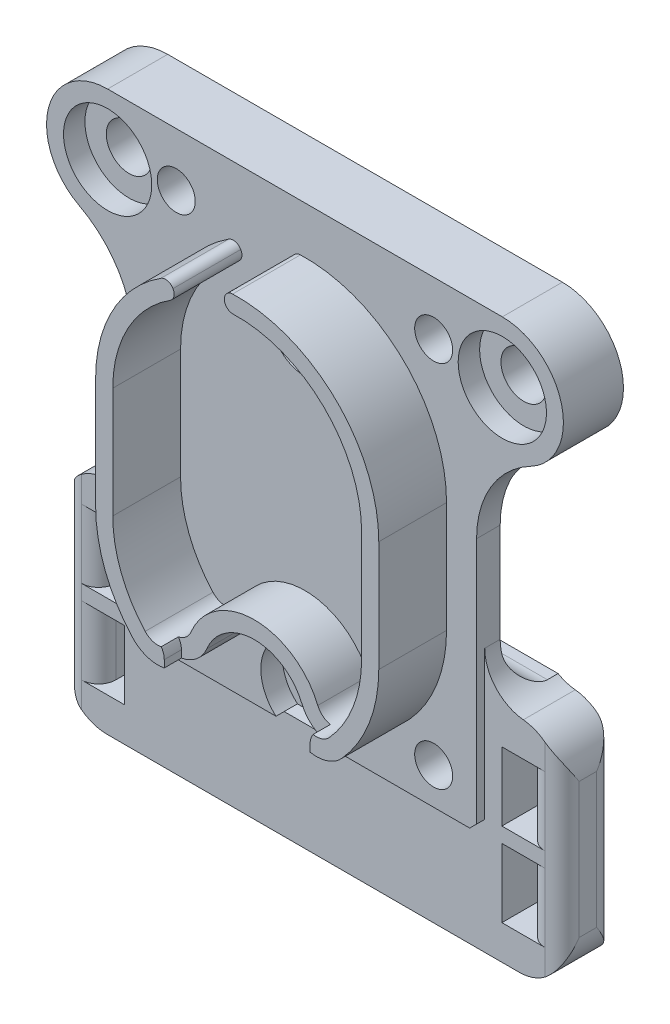
SolidWorks part; units mm, degrees
note: The reader was unsure of these and kept them because the rebuilt part matched: shared geometry of "Sketch12<3>".
ref_plane "Front Plane" through (0, 0, 0) normal (0, 0, 1) x (1, 0, 0)
ref_plane "Top Plane" through (0, 0, 0) normal (0, 1, 0) x (1, 0, 0)
ref_plane "Right Plane" through (0, 0, 0) normal (1, 0, 0) x (0, 0, -1)
sketch "Sketch1" plane through (0, 0, 0) normal (0, 0, 1) x (1, 0, 0)
  line L2 (55, 0) -> (-55, 0) construction
  line L4 (0, -8.5) -> (0, -21.398) construction
  line L6 (-5.5475, -31.3341) -> (-7.3967, -30.5721) construction
  line L15 (0, -9.2125) -> (0, 9.2125) construction
  line L16 (16.5, -8.5) -> (16.5, -21.398)
  line L17 (-16.5, -8.5) -> (-16.5, -21.398)
  line L18 (0, -8.5) -> (0, -21.398) construction
  line L19 (14.5, -8.5) -> (14.5, -21.398)
  line L20 (-14.5, -8.5) -> (-14.5, -21.398)
  line L21 (-12.2045, -32.5021) -> (-10.7252, -31.1561) construction
  line L22 (-10.7252, -31.1561) -> (-15.5979, -25.8005) construction
  line L23 (-7.3967, -30.5721) -> (-7.658, -31.2064) construction
  arc A23 (16.5, -8.5) -> (-16.5, -8.5) centre (0, -8.5) ccw
  arc A24 (-16.5, -21.398) -> (-12.2045, -32.5021) centre (0, -21.398) ccw
  arc A25 (14.5, -8.5) -> (-14.5, -8.5) centre (0, -8.5) ccw
  arc A26 (-14.5, -21.398) -> (-10.7252, -31.1561) centre (0, -21.398) ccw
  arc A27 (5.5475, -31.3341) -> (-5.5475, -31.3341) centre (0, -33.62) ccw
  arc A28 (7.3967, -30.5721) -> (-7.3967, -30.5721) centre (0, -33.62) ccw
  arc A29 (12.2045, -32.5021) -> (16.5, -21.398) centre (0, -21.398) ccw
  arc A30 (10.7252, -31.1561) -> (14.5, -21.398) centre (0, -21.398) ccw
  arc A31 (-5.5475, -31.3341) -> (-12.2045, -32.5021) centre (-9.2458, -29.8102) cw
  arc A32 (5.5475, -31.3341) -> (12.2045, -32.5021) centre (9.2458, -29.8102) ccw
  arc A33 (10.7252, -31.1561) -> (7.3967, -30.5721) centre (9.2458, -29.8102) cw
  arc A34 (-7.3967, -30.5721) -> (-10.7252, -31.1561) centre (-9.2458, -29.8102) cw
  point P2 (-8.5546, -33.75)
  point P5 (0, -21.398)
  point P10 (0, -21.398)
  point P31 (4.8342, -37.174)
  point P37 (0, 8)
  dimension "D1" = 33
  dimension "D2" = 2
  dimension "D8" = 6
  dimension "D9" = 33.75
  dimension "D5" = 2
  dimension "D4" = 2
  dimension "D6" = 4
  dimension "D3" = 33.62
  dimension "D7" = 8
extrude "Boss-Extrude1" add sketch "Sketch1" along normal blind 7.9
sketch "Sketch2" plane through (0, 0, 0) normal (0, 0, -1) x (-1, 0, 0)
  line L8 (19.201, -40) -> (-19.201, -40)
  line L13 (0, 9.2125) -> (0, -9.2125) construction
  line L14 (-19.201, -40) -> (-20, -39.201)
  line L15 (-20, -39.201) -> (-20, -10.39)
  line L16 (-23, 13.5) -> (23, 13.5)
  line L17 (0, 21.1933) -> (0, -47.0841) construction
  line L18 (4.345, 0) -> (-4.345, 0) construction
  line L19 (19.201, -40) -> (20, -39.201)
  line L20 (20, -39.201) -> (20, -10.39)
  arc A6 (-20, -10.39) -> (-26.3186, 0.0807) centre (-31.8349, -10.39) ccw
  arc A7 (-26.3186, 0.0807) -> (-23, 13.5) centre (-23, 6.38) cw
  arc A8 (20, -10.39) -> (26.3186, 0.0807) centre (31.8349, -10.39) cw
  arc A9 (26.3186, 0.0807) -> (23, 13.5) centre (23, 6.38) ccw
  point P16 (0, -40)
  point P22 (0, 13.5)
  dimension "D7" = 13.5
  dimension "D9" = 46
  dimension "D1" = 135
  dimension "D2" = 1.13
  dimension "D3" = 20
  dimension "D4" = 40
  dimension "D5" = 29.61
  dimension "D6" = 6.38
extrude "Boss-Extrude2" add sketch "Sketch2" along normal blind 7
sketch "Sketch4" plane through (0, 0, 0) normal (1, 0, 0) x (0, 0, -1)
  line L0 (12.75, -2.25) -> (5.75, -2.25)
  line L1 (2.75, -5.25) -> (2.75, -23.25)
  line L2 (5.75, -26.25) -> (12.75, -26.25)
  line L3 (12.75, -26.25) -> (12.75, -2.25)
  line L4 (0, 20.3925) -> (0, -20.3925) construction
  line L5 (8.525, 0) -> (-8.525, 0) construction
  arc A0 (5.75, -2.25) -> (2.75, -5.25) centre (5.75, -5.25) ccw
  arc A1 (2.75, -23.25) -> (5.75, -26.25) centre (5.75, -23.25) ccw
  dimension "D4" = 3
  dimension "D1" = 2.75
  dimension "D2" = 2.25
  dimension "D3" = 24
  dimension "D5" = 10
extrude "Cut-Extrude1" cut sketch "Sketch4" against normal through all both and the other way through all
sketch "Sketch5" plane through (0, 0, -7) normal (0, 0, -1) x (-1, 0, 0)
  line L0 (-23, 6.38) -> (23, 6.38) construction
  line L1 (0, 9.2125) -> (0, -9.2125) construction
  circle A0 centre (-23, 6.38) radius 3.9
  circle A1 centre (23, 6.38) radius 3.9
  arc A3 (-23, 13.5) -> (-26.3186, 0.0807) centre (-23, 6.38) ccw construction
  circle A4 centre (0, -36.12) radius 3.9
  point P4 (0, 6.38)
  dimension "D3" = 7.8
  dimension "D1" = 42.5
extrude "Boss-Extrude3" add sketch "Sketch5" along normal blind 1.25
sketch "Sketch6" plane through (0, 0, 7.9) normal (0, 0, 1) x (1, 0, 0)
  line L0 (0, -9.2125) -> (0, 9.2125) construction
  line L1 (-8.5, -40) -> (8.5, -40)
  line L3 (8.5, -40) -> (8.5, -32.9018)
  line L4 (-8.5, -40) -> (-8.5, -32.9018)
  line L6 (19.201, -40) -> (-19.201, -40) construction
  arc A0 (9.1452, -31.4306) -> (-9.1452, -31.4306) centre (0, -21.5) ccw
  arc A1 (8.5, -32.9018) -> (9.1452, -31.4306) centre (10.5, -32.9018) cw
  arc A2 (-8.5, -32.9018) -> (-9.1452, -31.4306) centre (-10.5, -32.9018) ccw
  dimension "D2" = 27
  dimension "D4" = 2
  dimension "D1" = 21.5
  dimension "D3" = 17
extrude "Cut-Extrude4" cut sketch "Sketch6" against normal blind 2
sketch "Sketch7" plane through (0, 0, 0) normal (0, 0, 1) x (1, 0, 0)
  line L0 (-15, 7.25) -> (15, 7.25) construction
  line L1 (0, -9.2125) -> (0, 9.2125) construction
  circle A0 centre (-15, 7.25) radius 2.2135
  circle A1 centre (15, 7.25) radius 2.2135
  circle A2 centre (15, -35.75) radius 2.2135
  circle A3 centre (-15, -35.75) radius 2.2135
  point P8 (0, 7.25)
  dimension "D1" = 4.4269
  dimension "D2" = 30
  dimension "D3" = 43
  dimension "D4" = 7.25
sketch "Sketch8" plane through (0, 0, 0) normal (0, 0, -1) x (-1, 0, 0)
  circle A0 centre (23, 6.38) radius 5.144
  circle A1 centre (-23, 6.38) radius 5.144
  circle A2 centre (0, -36.12) radius 5.144
  dimension "D1" = 10.288
extrude "Cut-Extrude6" cut sketch "Sketch8" along normal blind 2.5
fillet "Fillet1" radius 2.5 3 edges at (-19.1, 6.38, -7) (26.9, 6.38, -7) (0, -32.22, -7)
extrude "Cut-Extrude7" cut sketch "Sketch7" against normal blind 5
sketch "Sketch9" plane through (0, 0, 0) normal (0, 0, 1) x (1, 0, 0)
  circle A0 centre (23, 6.38) radius 2.6605
  circle A1 centre (-23, 6.38) radius 2.6605
  circle A2 centre (0, 0) radius 4
  circle A3 centre (23, 6.38) radius 5.144 construction
  circle A4 centre (-23, 6.38) radius 5.144 construction
  circle A5 centre (0, -36.12) radius 2.5
  dimension "D1" = 8
  dimension "D2" = 5.321
  dimension "D3" = 5
extrude "Cut-Extrude8" cut sketch "Sketch9" against normal through all both and the other way through all
sketch "Sketch10" [suppressed] plane through (0, 0, 0) normal (0, 0, 1) x (1, 0, 0)
  circle A0 centre (15, 7.25) radius 2.5
  circle A1 centre (23, 6.38) radius 4
  dimension "D1" = 5
  dimension "D2" = 8
sketch "Sketch11" plane through (0, 0, 0) normal (0, 0, 1) x (1, 0, 0)
  line L0 (-7.9879, 5.9376) -> (-6.9877, 4.2052)
  line L1 (-1.5, 7.9317) -> (-1.5, 5.9222)
  line L4 (0, -9.2125) -> (0, 9.2125) construction
  arc A0 (16.5, -8.5) -> (-16.5, -8.5) centre (0, -8.5) ccw construction
  arc A1 (14.5, -8.5) -> (-14.5, -8.5) centre (0, -8.5) ccw construction
  arc A2 (14.5, -8.5) -> (-14.5, -8.5) centre (0, -8.5) ccw construction
  arc A3 (-7.9879, 5.9376) -> (-1.5, 7.9317) centre (0, -8.5) cw
  arc A4 (-6.9877, 4.2052) -> (-1.5, 5.9222) centre (0, -8.5) cw
  arc A5 (14.5, -8.5) -> (-14.5, -8.5) centre (0, -8.5) ccw construction
  arc A6 (16.5, -8.5) -> (-16.5, -8.5) centre (0, -8.5) ccw construction
  dimension "D1" = 1.5
  dimension "D2" = 5.75
  dimension "D3" = 30
  dimension "D4" = 0
extrude "Cut-Extrude9" cut sketch "Sketch11" along normal through all
fillet "Fillet2" radius 1 4 edges at (-1.5, 5.9222, 3.95) (-6.9877, 4.2052, 3.95) (-7.9879, 5.9376, 3.95) (-1.5, 7.9317, 3.95)
ref_plane "Plane1" through (0, -52.62, 0) normal (0, -1, 0) x (-1, 0, 0)
sketch "Sketch12" plane through (0, 0, 0) normal (0, 0, 1) x (1, 0, 0)
  line L0 (23.5, -31.87) -> (23.5, -37.87) construction
  line L1 (-29, -52.62) -> (29, -52.62)
  line L2 (-29, -52.62) -> (-29, -26.87)
  line L4 (29, -52.62) -> (29, -26.87)
  line L5 (-29, -52.62) -> (29, -26.87) construction
  line L6 (-29, -26.87) -> (29, -52.62) construction
  line L7 (-22, -48.62) -> (-25, -48.62)
  line L8 (-22, -48.62) -> (-22, -40.62)
  line L9 (-22, -40.62) -> (-25, -40.62)
  line L10 (-25, -48.62) -> (-25, -40.62)
  line L11 (-22, -48.62) -> (-25, -40.62) construction
  line L12 (-22, -40.62) -> (-25, -48.62) construction
  line L13 (25, -38.87) -> (22, -38.87)
  line L14 (25, -38.87) -> (25, -30.87)
  line L15 (25, -30.87) -> (22, -30.87)
  line L16 (22, -38.87) -> (22, -30.87)
  line L17 (25, -38.87) -> (22, -30.87) construction
  line L18 (25, -30.87) -> (22, -38.87) construction
  line L19 (0, -9.2125) -> (0, 9.2125) construction
  line L20 (20, -10.39) -> (20, -39.201) construction
  line L21 (29, -26.87) -> (20, -26.87)
  line L22 (20, -26.87) -> (20, -39.201)
  line L23 (20, -39.201) -> (19.201, -40)
  line L24 (19.201, -40) -> (-19.201, -40)
  line L25 (-19.201, -40) -> (-20, -39.201)
  line L26 (-20, -39.201) -> (-20, -26.87)
  line L27 (-20, -39.201) -> (-20, -10.39) construction
  line L28 (-20, -26.87) -> (-29, -26.87)
  line L29 (0, -37.87) -> (0, -41.62) construction
  line L30 (52.8021, -37.87) -> (-140.1979, -37.87) construction
  line L31 (52.8021, -41.62) -> (-140.1979, -41.62) construction
  line L33 (52.8021, -31.87) -> (-140.1979, -31.87) construction
  line L34 (-22, -39.745) -> (22, -39.745) construction
  line L37 (-22, -38.87) -> (-25, -38.87)
  line L38 (-22, -38.87) -> (-22, -30.87)
  line L39 (-22, -30.87) -> (-25, -30.87)
  line L40 (-25, -38.87) -> (-25, -30.87)
  line L41 (22, -40.62) -> (25, -40.62)
  line L42 (22, -40.62) -> (22, -48.62)
  line L43 (22, -48.62) -> (25, -48.62)
  line L44 (25, -40.62) -> (25, -48.62)
  point P0 (0, -39.745)
  point P5 (-23.5, -44.62)
  point P10 (23.5, -34.87)
  point P20 (0, -52.62)
  point P39 (0, -39.745)
  point P40 (23.5, -34.87)
  point P48 (0, -39.745)
  dimension "D1" = 3
  dimension "D2" = 8
  dimension "D4" = 2
  dimension "D5" = 4
  dimension "D6" = 4
  dimension "D7" = 4
extrude "Boss-Extrude4" add sketch "Sketch12" against normal up to surface (7 mm away) contours L26 L28 L2 L1 L4 L21 L22 L23 L24 L25 L13 L16 L15 L14 L7 L10 L9 L8 | L10 L7 L8 L9
fillet "Fillet3" radius 5 2 edges at (-29, -26.87, -3.5) (29, -52.62, -3.5)
fillet "Fillet4" radius 5 2 edges at (29, -26.87, -3.5) (-29, -52.62, -3.5)
fillet "Fillet5" radius 5 2 edges at (20, -26.87, -3.5) (-20, -26.87, -3.5)
sketch "Sketch15" plane through (0, 0, 0) normal (0, 0, 1) x (1, 0, 0)
  line L0 (20, -16.1551) -> (20, -39.2)
  line L1 (20, -10.39) -> (20, -21.9201) construction
  line L2 (20, -39.2) -> (19.2, -40)
  line L3 (19.2, -40) -> (-19.2, -40)
  line L4 (-19.2, -40) -> (-20, -39.2)
  line L5 (-20, -39.2) -> (-20, -16.1551)
  line L6 (-20, -21.9201) -> (-20, -10.39) construction
  line L7 (-20, -16.1551) -> (-29, -16.245)
  line L8 (-47.1979, -16.245) -> (52.8021, -16.245) construction
  line L9 (-29, -16.245) -> (-29, -52.62)
  line L10 (-29, -52.62) -> (29, -52.62)
  line L11 (29, -52.62) -> (29, -16.1551)
  line L12 (29, -16.1551) -> (20, -16.1551)
  line L13 (29, -47.62) -> (29, -31.87) construction
  line L14 (-24, -52.62) -> (24, -52.62) construction
  line L15 (-29, -47.62) -> (-29, -31.87) construction
extrude "Cut-Extrude11" cut sketch "Sketch15" against normal up to vertex (0.95 mm away)
extrude "Cut-Extrude15" cut sketch "Sketch12<3>" against normal blind 35 contours L16 L13 L14 L15 | L10 L7 L8 L9
sketch "Sketch12<3>" plane through (0, 0, 0) normal (0, 0, 1) x (1, 0, 0) same geometry as "Sketch12"
fillet "Fillet7" radius 2 8 edges at (-25, -44.62, -0.95) (25, -34.87, -0.95) (-29, -39.745, -0.95) (29, -39.745, -0.95) (25, -44.62, -0.95) (-25, -34.87, -0.95) (-29, -39.745, -7) (29, -39.745, -7)
sketch "Sketch16" plane through (0, 0, 0) normal (0, 0, 1) x (1, 0, 0)
  circle A0 centre (0, -36.12) radius 5.14
  circle A1 centre (0, -36.12) radius 3.65
  dimension "D1" = 10.28
  dimension "D2" = 7.3
extrude "Cut-Extrude16" cut sketch "Sketch16" against normal through all contours A1
